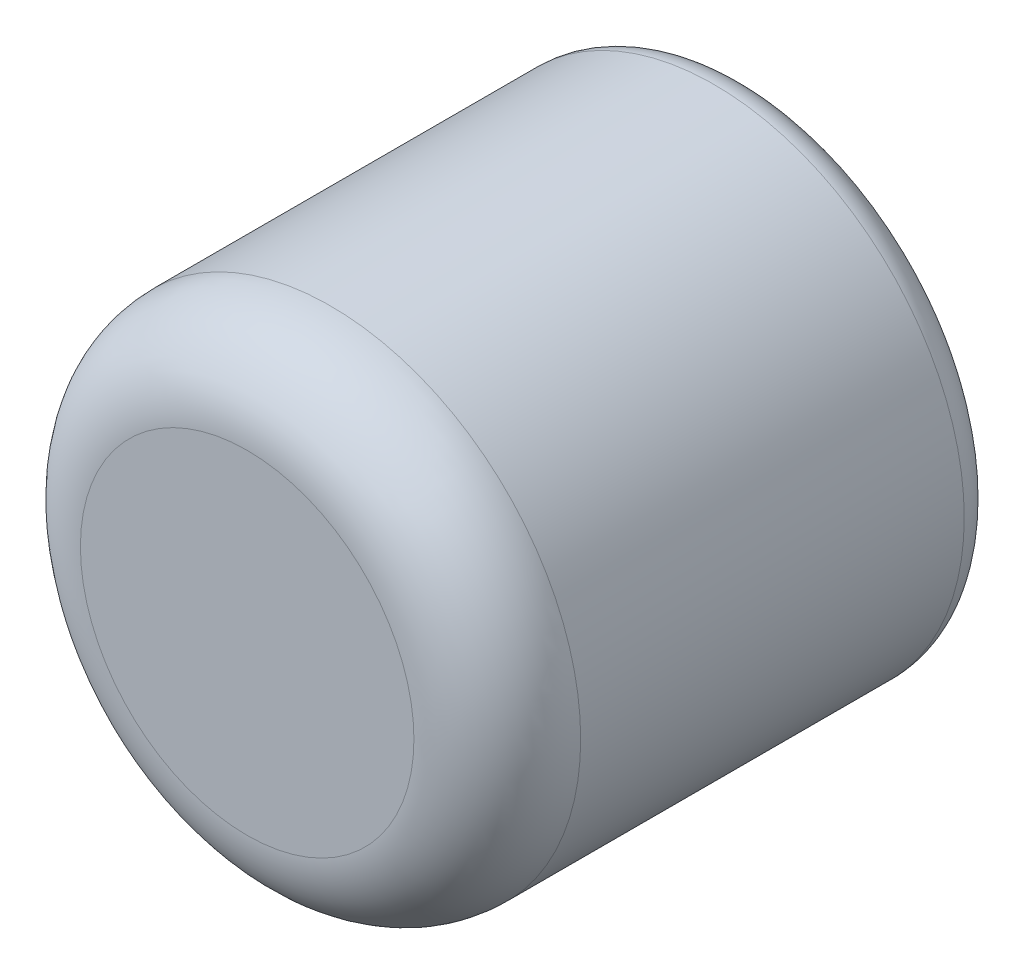
SolidWorks part; units mm, degrees
material "1023 Carbon Steel Sheet (SS)"
ref_plane "Front Plane" through (0, 0, 0) normal (0, 0, 1) x (1, 0, 0)
ref_plane "Top Plane" through (0, 0, 0) normal (0, 1, 0) x (1, 0, 0)
ref_plane "Right Plane" through (0, 0, 0) normal (1, 0, 0) x (0, 0, -1)
sketch "Sketch1" plane through (0, 0, 0) normal (0, 0, 1) x (1, 0, 0)
  circle A0 centre (0, 0) radius 10.4
  circle A1 centre (0, 0) radius 15
  dimension "D1" = 20.8
  dimension "D2" = 30
extrude "Boss-Extrude1" add sketch "Sketch1" along normal blind 30 contours A1 A0 | A0 region at (0, 0, 0) region at (-14.5757, 0, 0)
extrude "Cut-Extrude1" cut sketch "Sketch1<3>" along normal blind 27 contours A0 region at (0, 0, 0)
sketch "Sketch1<3>" plane through (0, 0, 0) normal (0, 0, 1) x (1, 0, 0) same geometry as "Sketch1"
thread "Thread1" pitch 2 method extrude profile "Thread Profile1" start angle 0, offset 0, length 20, pitch 2, diameter 20.8
ref_plane "Plane1" through (10.4, 0, 0) normal (0, -1, 0) x (1, 0, 0)
sketch "Thread Profile1" plane through (10.4, 0, 0) normal (0, -1, 0) x (1, 0, 0)
  line L0 (0, 0) -> (0, 2) construction
  line L11 (0, 0) -> (0, 1.75)
  line L12 (0, 1.75) -> (-1.0825, 1.125)
  line L13 (-1.0825, 1.125) -> (-1.0825, 0.625)
  line L15 (-1.0825, 0.625) -> (0, 0)
  line L17 (-1.0825, 0.875) -> (0, 0.875) construction
  point P2 (0, 0)
  dimension "Pitch" = 2
  dimension "Profile_Angle" = 60
  dimension "Profile_Land" = 0.5
  dimension "Profile_Height" = 1.0825
fillet "Fillet1" radius 5 1 edges at (15, 0, 30)
fillet "Fillet2" radius 2 1 edges at (15, 0, 0)
